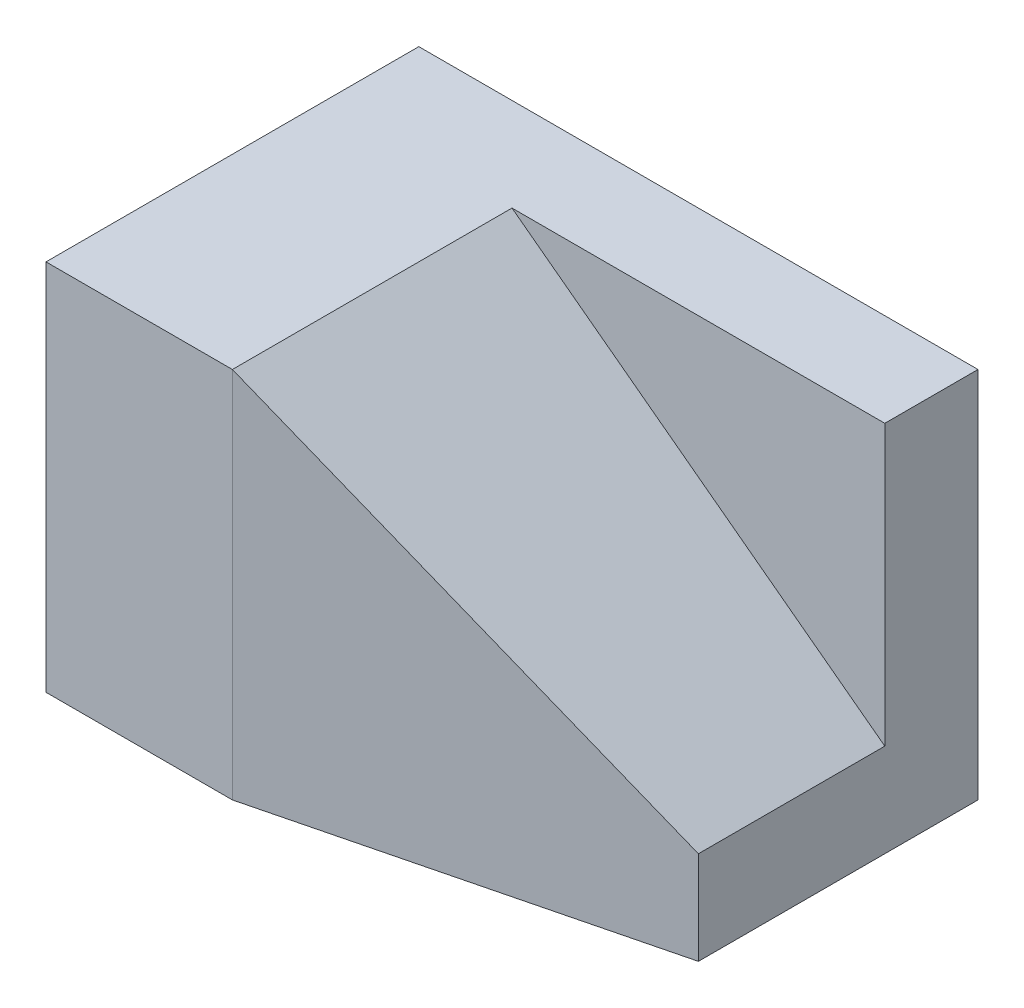
SolidWorks part; units mm, degrees
ref_plane "前基準面" through (0, 0, 0) normal (0, 0, 1) x (1, 0, 0)
ref_plane "上基準面" through (0, 0, 0) normal (0, 1, 0) x (1, 0, 0)
ref_plane "右基準面" through (0, 0, 0) normal (1, 0, 0) x (0, 0, -1)
sketch "草圖1" plane through (0, 0, 0) normal (0, 1, 0) x (1, 0, 0)
  line L0 (-5, -10) -> (15, -5)
  line L1 (15, 10) -> (-15, 10)
  line L2 (15, 10) -> (15, -5)
  line L3 (-5, -10) -> (-15, -10)
  line L4 (-15, 10) -> (-15, -10)
  line L5 (15, 10) -> (-15, -10) construction
  line L6 (9.5455, -6.3636) -> (-15, 10) construction
  line L8 (15, -5) -> (15, 5)
  line L9 (15, 5) -> (-5, 5)
  line L10 (-5, -10) -> (-5, 5)
  point P0 (0, 0)
  dimension "D1" = 20
  dimension "D2" = 30
  dimension "D3" = 5
  dimension "D4" = 10
extrude "填料-伸長1" add sketch "草圖1" along normal blind 20 contours L10 L0 L2 L9 region at (4.3333, 0, 1.3333)
extrude "填料-伸長2" add sketch "草圖1<3>" along normal blind 20 contours L3 L10 L9 L2 L1 L4 region at (-10, 0, 9.6394)
sketch "草圖1<3>" plane through (0, 0, 0) normal (0, 1, 0) x (1, 0, 0) same geometry as "草圖1"
sketch "草圖2" plane through (0, 0, 10) normal (0, 0, 1) x (1, 0, 0)
  line L0 (-5, 20) -> (15, 5)
  line L1 (15, 20) -> (15, 0) construction
  line L2 (15, 5) -> (15, 20)
  line L3 (15, 20) -> (-5, 20)
  dimension "D1" = 15
extrude "除料-伸長1" cut sketch "草圖2" against normal blind 15
scale "縮放比例1" scale about centroid uniform scaling yes scale factor 0.2
